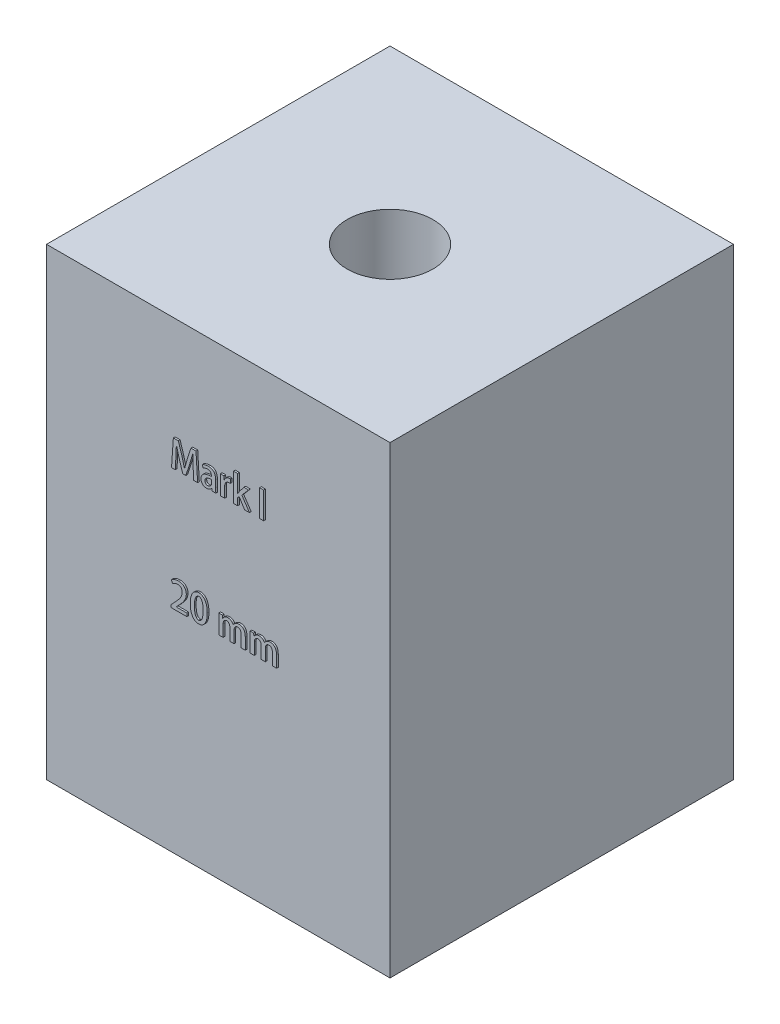
SolidWorks part; units mm, degrees
ref_plane "Alzado" through (0, 0, 0) normal (0, 0, 1) x (1, 0, 0)
ref_plane "Planta" through (0, 0, 0) normal (0, 1, 0) x (1, 0, 0)
ref_plane "Vista lateral" through (0, 0, 0) normal (1, 0, 0) x (0, 0, -1)
sketch "Croquis1" plane through (0, 0, 0) normal (0, 1, 0) x (1, 0, 0)
  line L1 (-10, 10) -> (10, 10)
  line L2 (-10, 10) -> (-10, -10)
  line L3 (-10, -10) -> (10, -10)
  line L4 (10, 10) -> (10, -10)
  line L5 (-10, 10) -> (10, -10) construction
  line L6 (-10, -10) -> (10, 10) construction
  circle A0 centre (0, 0) radius 2.5
  point P0 (0, 0)
  dimension "D1" = 5
  dimension "D2" = 20
extrude "Saliente-Extruir1" add sketch "Croquis1" along normal blind 27
sketch "Croquis2" plane through (0, 0, 10) normal (0, 0, 1) x (1, 0, 0)
  text T0 "Mark I\r\n \r\n20 mm" font "@Adobe Heiti Std R" height in points 5
split line "Línea de partición1"
extrude "Saliente-Extruir2" add sketch "Croquis2<2>" along normal blind 0.1
sketch "Croquis2<2>" plane through (0, 0, 10) normal (0, 0, 1) x (1, 0, 0) same geometry as "Croquis2"
